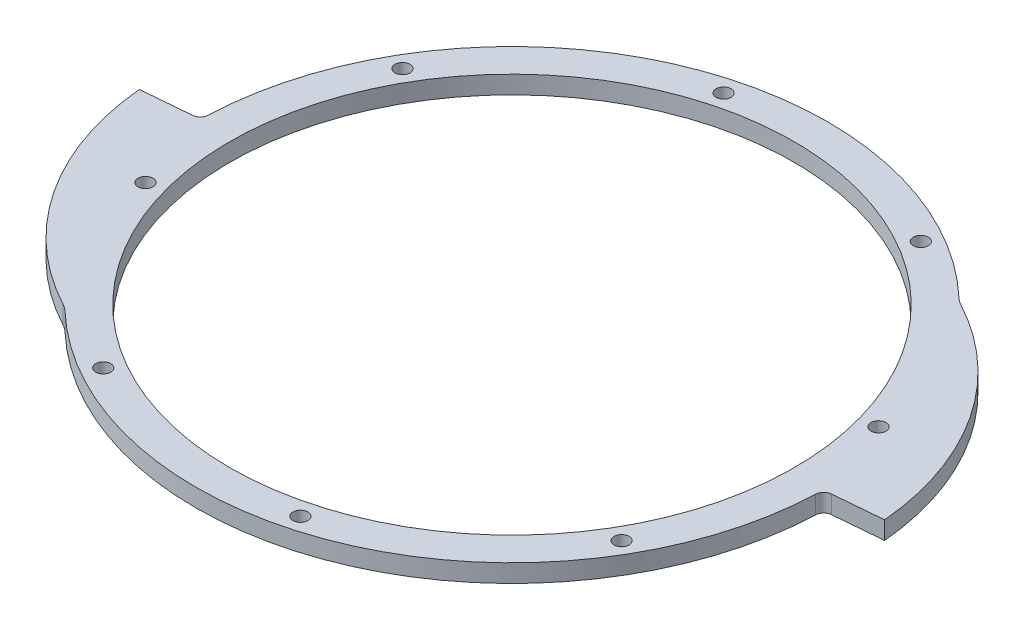
SolidWorks part; units mm, degrees
material "Alloy Steel"
ref_plane "Front Plane" through (0, 0, 0) normal (0, 0, 1) x (1, 0, 0)
ref_plane "Top Plane" through (0, 0, 0) normal (0, 1, 0) x (1, 0, 0)
ref_plane "Right Plane" through (0, 0, 0) normal (1, 0, 0) x (0, 0, -1)
sketch "Sketch1" plane through (0, 0, 0) normal (0, 1, 0) x (1, 0, 0)
  line L0 (0, 0) -> (-132, 0) construction
  line L1 (-132.0082, 0.0941) -> (-134.7743, 31.7103) construction
  line L2 (-111.9863, 1.751) -> (-132, 0)
  line L3 (-132, 0) -> (-132, 32.0934) construction
  line L4 (-129.3938, 0) -> (-182.8754, 0) construction
  line L5 (-112, 0) -> (-132, 0) construction
  line L6 (-79.4774, -79.4774) -> (0, 0) construction
  circle A0 centre (0, 0) radius 100
  arc A10 (-132, 0) -> (-79.4774, -79.4774) centre (-32.4231, 8.7118) ccw
  arc A11 (-79.4774, -79.4774) -> (-77.2845, -81.0624) centre (-84.1849, -88.3001) cw
  arc A12 (-77.2845, -81.0624) -> (-111.9863, 1.751) centre (0, 0) ccw
  point P7 (-113.684, 0)
  point P13 (0, 0)
  dimension "D1" = 200
  dimension "D6" = 10
  dimension "D4" = 5
  dimension "D7" = 45
  dimension "D2" = 12
  dimension "D3" = 5
  dimension "D5" = 20
extrude "Boss-Extrude1" add sketch "Sketch1" along normal mid plane 6.35
fillet "Fillet1" radius 3 1 edges at (-111.9863, 0, -1.751)
pattern_circular "CirPattern1" count 2 over 360 about axis through (0, 3.175, 0) along (0, -1, 0) of "Boss-Extrude1", "Fillet1" reverse direction yes
sketch "Sketch2" plane through (0, 3.175, 0) normal (0, 1, 0) x (1, 0, 0)
  line L0 (-102.3881, -27.4348) -> (0, 0) construction
  line L1 (0, 0) -> (-106, 0) construction
  circle A0 centre (-102.3881, -27.4348) radius 2.65
  circle A2 centre (0, 0) radius 106 construction
  circle A3 centre (0, 0) radius 100 construction
  dimension "D3" = 5.3
  dimension "D1" = 106
  dimension "D2" = 6
  dimension "D4" = 15
extrude "Cut-Extrude1" cut sketch "Sketch2" against normal through all
pattern_circular "CirPattern2" count 8 over 360 about axis through (0, 3.175, 0) along (0, -1, 0) of "Cut-Extrude1"
equation "\"ring_id\"=200"
equation "\"D1@Sketch1\"=\"ring_id\""
equation "\"D2@Sketch2\"=\"D2@Sketch1\"/2"
